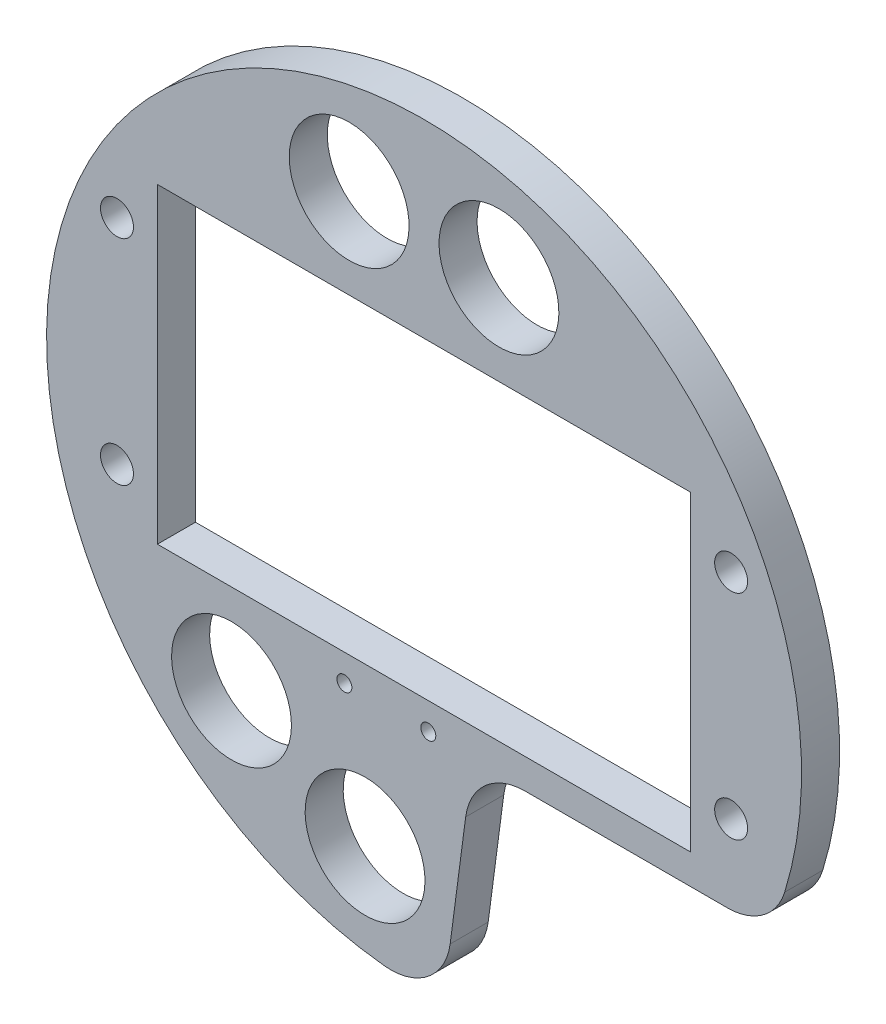
SolidWorks part; units mm, degrees
material "ABS"
ref_plane "Front Plane" through (0, 0, 0) normal (0, 0, 1) x (1, 0, 0)
ref_plane "Top Plane" through (0, 0, 0) normal (0, 1, 0) x (1, 0, 0)
ref_plane "Right Plane" through (0, 0, 0) normal (1, 0, 0) x (0, 0, -1)
ref_plane "Plane1" through (0, 0, -110.625) normal (0, 0, -1) x (-1, 0, 0)
sketch "Sketch2" plane through (0, 0, -110.625) normal (0, 0, -1) x (-1, 0, 0)
  line L0 (0, 63) -> (0, -63) construction
  line L1 (44.5, 5.3438) -> (-44.5, 5.3438) construction
  line L2 (44.5, -20.6562) -> (-44.5, -20.6562)
  line L3 (44.5, -20.6562) -> (44.5, 31.3438)
  line L4 (44.5, 31.3438) -> (-44.5, 31.3438)
  line L5 (-44.5, -20.6562) -> (-44.5, 31.3438)
  line L6 (44.5, -20.6562) -> (-44.5, 31.3438) construction
  line L7 (44.5, 31.3438) -> (-44.5, -20.6562) construction
  line L8 (12.5, 46.3438) -> (-12.5, 46.3438) construction
  line L9 (-4.3574, -54.0131) -> (-6.946, -34.3509)
  line L10 (-16.8605, -25.6562) -> (-50.6348, -25.6562)
  line L11 (51.25, 23.184) -> (51.25, -12.4964) construction
  line L12 (-51.25, 23.184) -> (-51.25, -12.4964) construction
  line L13 (-51.25, -12.4964) -> (51.25, -12.4964) construction
  line L14 (51.25, 23.184) -> (-51.25, 23.184) construction
  line L15 (13.2914, -25.1562) -> (-0.7086, -25.1562) construction
  line L16 (17.2914, -22.1562) -> (-4.7086, -22.1562) construction
  line L17 (17.7914, -22.6562) -> (17.7914, -36.0562) construction
  line L18 (17.7914, -36.0562) -> (-5.2086, -36.0562) construction
  line L19 (-5.2086, -22.6562) -> (-5.2086, -36.0562) construction
  line L20 (6.2914, -22.1562) -> (6.2914, -36.0562) construction
  circle A0 centre (0, 0) radius 63.5 construction
  arc A1 (6.6055, -62.6528) -> (-60.1885, -18.6102) centre (0, 0) ccw
  circle A2 centre (12.5, 46.3438) radius 15 construction
  circle A3 centre (12.5, 46.3438) radius 10
  circle A4 centre (-12.5, 46.3438) radius 10
  circle A5 centre (32.1347, -35.6562) radius 10
  circle A6 centre (32.1347, -35.6562) radius 15 construction
  circle A7 centre (9.846, -46.9793) radius 10
  circle A8 centre (9.846, -46.9793) radius 15 construction
  arc A9 (-57.5392, -25.6562) -> (-3.1849, -62.9194) centre (0, 0) ccw construction
  arc A10 (-50.6348, -25.6562) -> (-60.1885, -18.6102) centre (-50.6348, -15.6562) cw
  arc A11 (-6.946, -34.3509) -> (-16.8605, -25.6562) centre (-16.8605, -35.6562) ccw
  arc A12 (-4.3574, -54.0131) -> (6.6055, -62.6528) centre (5.557, -52.7079) ccw
  circle A13 centre (51.25, 23.184) radius 2.75
  circle A14 centre (51.25, -12.4964) radius 2.75
  circle A15 centre (-51.25, -12.4964) radius 2.75
  circle A16 centre (-51.25, 23.184) radius 2.75
  circle A17 centre (51.25, 23.184) radius 6.75 construction
  circle A18 centre (13.2914, -25.1562) radius 1.25
  circle A19 centre (-0.7086, -25.1562) radius 1.25
  arc A20 (-4.7086, -22.1562) -> (-5.2086, -22.6562) centre (-4.7086, -22.6562) ccw construction
  arc A21 (17.2914, -22.1562) -> (17.7914, -22.6562) centre (17.2914, -22.6562) cw construction
  point P0 (0, 0)
  point P8 (0, 5.3438)
  point P40 (0, 23.184)
  point P42 (51.25, 5.3438)
  point P57 (6.2914, -25.1562)
  point P60 (-5.2086, -22.1562)
  point P63 (17.7914, -22.1562)
  dimension "D1" = 127
  dimension "D2" = 0.5
  dimension "D5" = 5
  dimension "D6" = 20
  dimension "D9" = 10
  dimension "D10" = 5.5
  dimension "D11" = 4
  dimension "D14" = 2.5
  dimension "D17" = 0.5
  dimension "D3" = 89
  dimension "D4" = 52
  dimension "D7" = 5
  dimension "D8" = 7.5
  dimension "D12" = 23
  dimension "D13" = 13.9
  dimension "D15" = 3
  dimension "D16" = 14
  dimension "D18" = 1.5
  dimension "D19" = 1.5
extrude "Boss-Extrude1" add sketch "Sketch2" against normal blind 6.35
